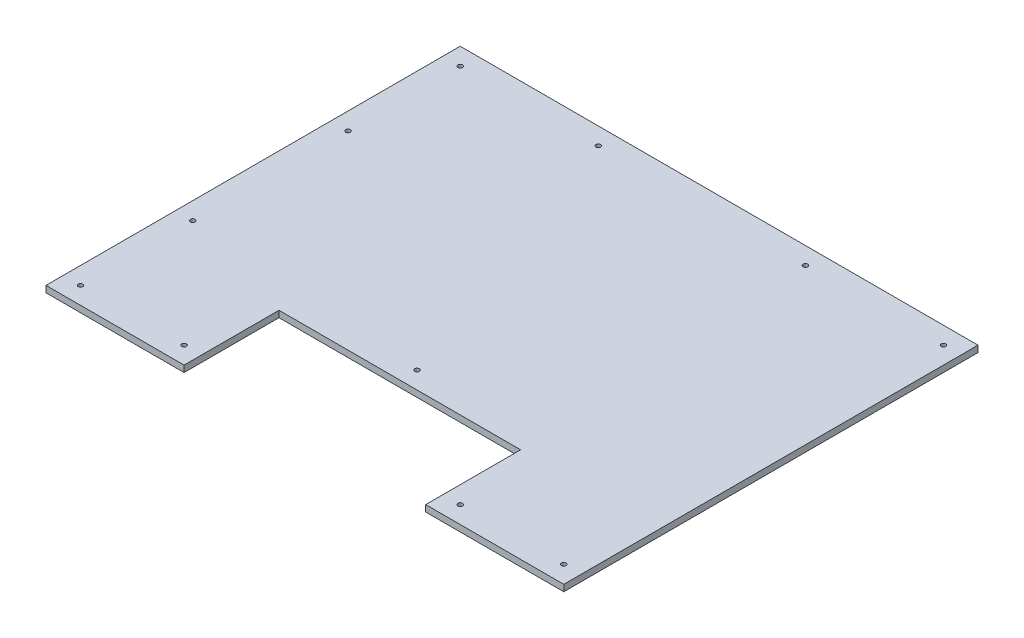
SolidWorks part; units mm, degrees
material "6061 Alloy"
ref_plane "Front Plane" through (0, 0, 0) normal (0, 0, 1) x (1, 0, 0)
ref_plane "Top Plane" through (0, 0, 0) normal (0, 1, 0) x (1, 0, 0)
ref_plane "Right Plane" through (0, 0, 0) normal (1, 0, 0) x (0, 0, -1)
sketch "Sketch1" plane through (0, 0, 0) normal (0, 1, 0) x (1, 0, 0)
  line L0 (0, 0) -> (0, -152.4) construction
  line L1 (-190.5, -152.4) -> (-88.9, -152.4)
  line L2 (-190.5, -152.4) -> (-190.5, 152.4)
  line L3 (-190.5, 152.4) -> (190.5, 152.4)
  line L4 (190.5, -152.4) -> (190.5, 152.4)
  line L5 (-190.5, -152.4) -> (190.5, 152.4) construction
  line L6 (-190.5, 152.4) -> (190.5, -152.4) construction
  line L8 (-88.9, -152.4) -> (-88.9, -82.55)
  line L9 (-88.9, -82.55) -> (88.9, -82.55)
  line L10 (88.9, -152.4) -> (88.9, -82.55)
  line L11 (88.9, -152.4) -> (190.5, -152.4)
  point P0 (0, 0)
  dimension "D1" = 304.8
  dimension "D2" = 381
  dimension "D3" = 69.85
  dimension "D4" = 177.8
extrude "Boss-Extrude1" add sketch "Sketch1" along normal blind 4.7625
sketch "Sketch2" plane through (0, 4.7625, 0) normal (0, 1, 0) x (1, 0, 0)
  line L0 (-177.8, 152.4) -> (-177.8, -152.4) construction
  line L1 (190.5, 152.4) -> (-190.5, 152.4) construction
  line L2 (-190.5, -152.4) -> (-88.9, -152.4) construction
  line L3 (-190.5, -139.7) -> (190.5, -139.7) construction
  line L4 (-190.5, 152.4) -> (-190.5, -152.4) construction
  line L5 (190.5, -152.4) -> (190.5, 152.4) construction
  line L6 (-190.5, 139.7) -> (190.5, 139.7) construction
  line L7 (177.8, 152.4) -> (177.8, -152.4) construction
  line L8 (-101.6, -152.4) -> (-101.6, -69.85) construction
  line L9 (-190.5, -152.4) -> (-88.9, -152.4) construction
  line L10 (-101.6, -69.85) -> (101.6, -69.85) construction
  line L11 (101.6, -69.85) -> (101.6, -152.4) construction
  line L12 (88.9, -152.4) -> (190.5, -152.4) construction
  line L13 (-88.9, -152.4) -> (-88.9, -82.55) construction
  line L14 (88.9, -82.55) -> (88.9, -152.4) construction
  line L15 (-88.9, -82.55) -> (88.9, -82.55) construction
  line L16 (177.8, 0) -> (-177.8, 0) construction
  line L17 (0, 139.7) -> (0, 0) construction
  point P16 (0, 0)
  point P20 (-177.8, -57.15)
  point P21 (-177.8, 57.15)
  point P22 (-76.2, 139.7)
  point P24 (76.2, 139.7)
  point P38 (-88.9, -117.475)
  point P43 (0, -69.85)
  point P44 (-177.8, 139.7)
  point P45 (177.8, 139.7)
  point P46 (177.8, -139.7)
  point P47 (101.6, -139.7)
  point P48 (-101.6, -139.7)
  point P49 (-177.8, -139.7)
  dimension "D1" = 12.7
  dimension "D2" = 12.7
  dimension "D3" = 12.7
  dimension "D4" = 12.7
  dimension "D9" = 12.7
  dimension "D10" = 12.7
  dimension "D11" = 12.7
  dimension "D8" = 114.3
  dimension "D7" = 152.4
hole_wizard "M3 Clearance Hole1" positions "3DSketch1" profile "Sketch3" hole size "M3" standard "ANSI Metric" end condition through all
sketch3d "3DSketch1"
  point P13 (-76.2, 4.7625, -139.7)
  point P19 (76.2, 4.7625, -139.7)
  point P43 (0, 4.7625, 69.85)
  point P49 (-101.6, 4.7625, 139.7)
  point P52 (-177.8, 4.7625, 139.7)
  point P55 (-177.8, 4.7625, -139.7)
  point P58 (177.8, 4.7625, -139.7)
  point P61 (177.8, 4.7625, 139.7)
  point P64 (101.6, 4.7625, 139.7)
  point P74 (-177.8, 4.7625, -57.15)
  point P77 (-177.8, 4.7625, 57.15)
sketch "Sketch3" plane through (-76.2, 4.7625, -139.7) normal (1, 0, 0) x (0, 0, 1)
  line L0 (0, 0) -> (0, 4.7625)
  line L1 (0, 4.7625) -> (1.7, 4.7625)
  line L2 (1.7, 4.7625) -> (1.7, 0)
  line L5 (1.7, 0) -> (0, 0)
  line L11 (0, -6.35) -> (0, 107.95) construction
  dimension "Thru Hole Dia." = 3.4
  dimension "Thru Hole Depth" = 4.7625
equation "\"D3@Sketch2\"=\"D1@Sketch2\""
equation "\"D4@Sketch2\"=\"D2@Sketch2\""
equation "\"D9@Sketch2\"=\"D1@Sketch2\""
equation "\"D10@Sketch2\"=\"D1@Sketch2\""
equation "\"D11@Sketch2\"=\"D1@Sketch2\""
equation "\"D2@Sketch2\"=\"D1@Sketch2\""
